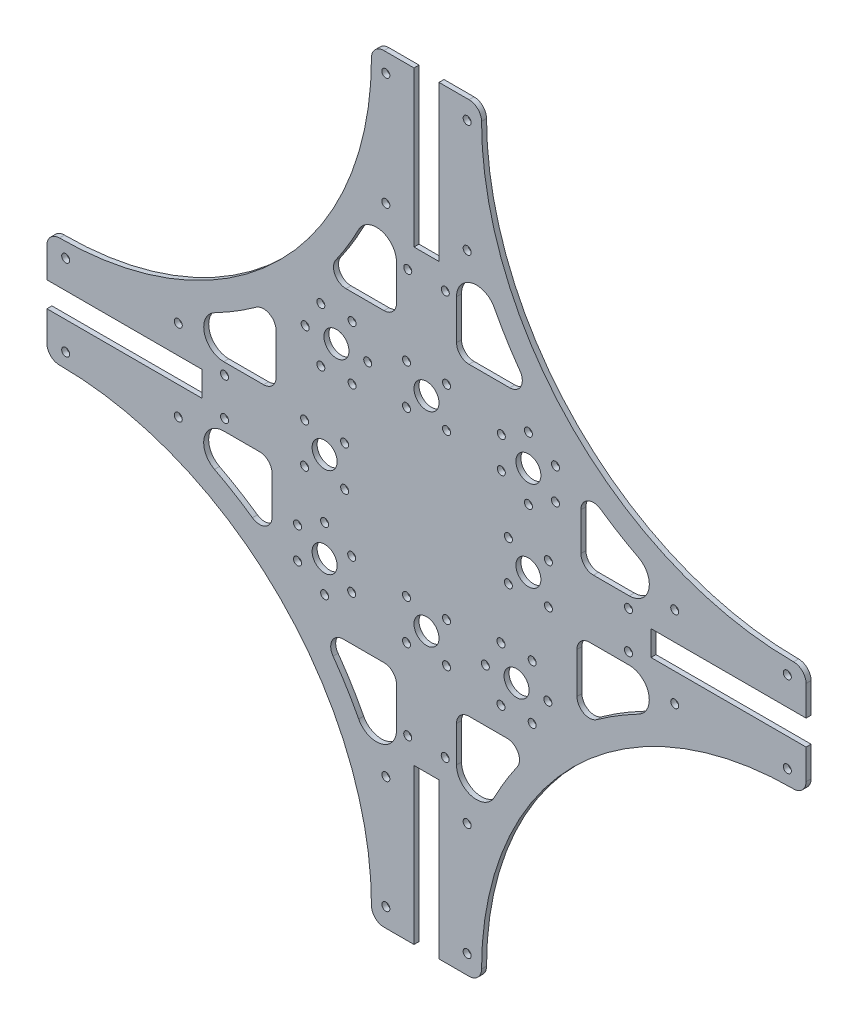
SolidWorks part; units mm, degrees
ref_plane "Front Plane" through (0, 0, 0) normal (0, 0, 1) x (1, 0, 0)
ref_plane "Top Plane" through (0, 0, 0) normal (0, 1, 0) x (1, 0, 0)
ref_plane "Right Plane" through (0, 0, 0) normal (1, 0, 0) x (0, 0, -1)
sketch "Sketch1" plane through (0, 0, 0) normal (0, 0, 1) x (1, 0, 0)
  line L0 (71.229, -85.5827) -> (71.229, -51.5827)
  line L1 (66.229, -90.5827) -> (-5.6672, -90.5827)
  line L2 (66.229, -46.5827) -> (-5.6672, -46.5827)
  line L3 (-102.5004, -215.312) -> (-102.5004, -143.4158)
  line L4 (-97.5004, -220.312) -> (-63.5004, -220.312)
  line L5 (-58.5004, -215.312) -> (-58.5004, -143.4158)
  line L6 (-227.2297, -46.5827) -> (-155.3335, -46.5827)
  line L7 (-232.2297, -51.5827) -> (-232.2297, -85.5827)
  line L8 (-227.2297, -90.5827) -> (-155.3335, -90.5827)
  line L9 (-58.5004, 78.1467) -> (-58.5004, 6.2505)
  line L10 (-63.5004, 83.1467) -> (-97.5004, 83.1467)
  line L11 (-102.5004, 78.1467) -> (-102.5004, 6.2505)
  arc A0 (-97.5004, -220.312) -> (-102.5004, -215.312) centre (-97.5004, -215.312) cw
  arc A1 (71.229, -51.5827) -> (66.229, -46.5827) centre (66.229, -51.5827) ccw
  arc A2 (71.229, -85.5827) -> (66.229, -90.5827) centre (66.229, -85.5827) cw
  arc A3 (-5.6672, -46.5827) -> (-58.5004, 6.2505) centre (-80.5004, -68.5827) ccw
  arc A4 (-63.5004, -220.312) -> (-58.5004, -215.312) centre (-63.5004, -215.312) ccw
  arc A5 (-232.2297, -51.5827) -> (-227.2297, -46.5827) centre (-227.2297, -51.5827) cw
  arc A6 (-232.2297, -85.5827) -> (-227.2297, -90.5827) centre (-227.2297, -85.5827) ccw
  arc A7 (-63.5004, 83.1467) -> (-58.5004, 78.1467) centre (-63.5004, 78.1467) cw
  arc A8 (-97.5004, 83.1467) -> (-102.5004, 78.1467) centre (-97.5004, 78.1467) ccw
  arc A9 (-102.5004, 6.2505) -> (-155.3335, -46.5827) centre (-80.5004, -68.5827) ccw
  arc A10 (-155.3335, -90.5827) -> (-102.5004, -143.4158) centre (-80.5004, -68.5827) ccw
  arc A11 (-58.5004, -143.4158) -> (-5.6672, -90.5827) centre (-80.5004, -68.5827) ccw
  point P14 (-80.5004, -68.5827)
  point P42 (-80.5004, -68.5827)
  dimension "D1" = 4
extrude "Boss-Extrude1" add sketch "Sketch1" along normal blind 2
sketch "Sketch2" plane through (0, 0, 2) normal (0, 0, 1) x (1, 0, 0)
  circle A1 centre (-39.771, -68.5827) radius 5
  circle A2 centre (-80.5004, -109.312) radius 5
  circle A3 centre (-121.2297, -68.5827) radius 5
  circle A4 centre (-80.5004, -27.8533) radius 5
  point P9 (-80.5004, -68.5827)
  point P19 (-80.5004, -68.5827)
  dimension "D1" = 4
  dimension "D3" = 10
  dimension "D2" = 57.6
extrude "Cut-Extrude1" cut sketch "Sketch2" against normal blind 2
ref_axis "A1" through (-80.5004, -109.312, 0) along (0, 0, 1)
ref_axis "A2" through (-39.771, -68.5827, 0) along (0, 0, 1)
ref_axis "A3" through (-121.2297, -68.5827, 0) along (0, 0, 1)
ref_axis "A4" through (-80.5004, -27.8533, 0) along (0, 0, 1)
ref_axis "Ось апп" through (-80.5004, -68.5827, 62.4812) along (0, 0, -1)
sketch "Sketch3" plane through (0, 0, 2) normal (0, 0, 1) x (1, 0, 0)
  line L0 (-39.771, -68.5827) -> (-39.771, -13.6018) construction
  circle A0 centre (-39.771, -32.5827) radius 5
  circle A3 centre (-39.771, -20.0827) radius 1.6
  circle A4 centre (-28.9457, -26.3327) radius 1.6
  circle A5 centre (-28.9457, -38.8327) radius 1.6
  circle A6 centre (-39.771, -45.0827) radius 1.6
  circle A7 centre (-50.5963, -38.8327) radius 1.6
  circle A8 centre (-50.5963, -26.3327) radius 1.6
  circle A21 centre (-39.771, -32.5827) radius 12.5 construction
  circle A22 centre (-44.5004, -109.312) radius 5
  circle A23 centre (-32.0004, -109.312) radius 1.6
  circle A24 centre (-38.2504, -120.1373) radius 1.6
  circle A25 centre (-50.7504, -120.1373) radius 1.6
  circle A26 centre (-57.0004, -109.312) radius 1.6
  circle A27 centre (-50.7504, -98.4867) radius 1.6
  circle A28 centre (-38.2504, -98.4867) radius 1.6
  circle A29 centre (-44.5004, -109.312) radius 12.5 construction
  circle A30 centre (-121.2297, -104.5827) radius 5
  circle A31 centre (-121.2297, -117.0827) radius 1.6
  circle A32 centre (-132.055, -110.8327) radius 1.6
  circle A33 centre (-132.055, -98.3327) radius 1.6
  circle A34 centre (-121.2297, -92.0827) radius 1.6
  circle A35 centre (-110.4044, -98.3327) radius 1.6
  circle A36 centre (-110.4044, -110.8327) radius 1.6
  circle A37 centre (-121.2297, -104.5827) radius 12.5 construction
  circle A38 centre (-116.5004, -27.8533) radius 5
  circle A39 centre (-129.0004, -27.8533) radius 1.6
  circle A40 centre (-122.7504, -17.028) radius 1.6
  circle A41 centre (-110.2504, -17.028) radius 1.6
  circle A42 centre (-104.0004, -27.8533) radius 1.6
  circle A43 centre (-110.2504, -38.6786) radius 1.6
  circle A44 centre (-122.7504, -38.6786) radius 1.6
  circle A45 centre (-116.5004, -27.8533) radius 12.5 construction
  point P9 (-80.5004, -68.5827)
  point P15 (-80.5004, -68.5827)
  point P28 (-39.771, -32.5827)
  point P40 (-80.5004, -68.5827)
  point P69 (-44.5004, -109.312)
  point P85 (-121.2297, -104.5827)
  point P101 (-116.5004, -27.8533)
  point P103 (-80.5004, -68.5827)
  dimension "D1" = 36
  dimension "D3" = 10
  dimension "D6" = 12.5
  dimension "D9" = 4
  dimension "D7" = 6
extrude "Cut-Extrude2" cut sketch "Sketch3" against normal blind 2
sketch "Sketch4" plane through (0, 0, 0) normal (0, 0, -1) x (-1, 0, 0)
  line L0 (232.2297, -63.5827) -> (170.2297, -63.5827)
  line L1 (232.2297, -51.5827) -> (232.2297, -85.5827) construction
  line L2 (170.2297, -63.5827) -> (170.2297, -73.5827)
  line L3 (170.2297, -73.5827) -> (232.2297, -73.5827)
  line L4 (232.2297, -73.5827) -> (232.2297, -63.5827)
  line L6 (227.2297, -90.5827) -> (155.3335, -90.5827) construction
  line L7 (155.3335, -46.5827) -> (227.2297, -46.5827) construction
  line L8 (102.5004, -143.4158) -> (58.5004, 6.2505) construction
  point P13 (80.5004, -68.5827)
  dimension "D1" = 17
  dimension "D2" = 17
  dimension "D3" = 62
extrude "Cut-Extrude3" cut sketch "Sketch4" against normal blind 2
pattern_circular "CirPattern1" count 4 over 360 about axis through (-80.5004, -68.5827, 62.4812) along (0, 0, -1) of "Cut-Extrude3"
sketch "Sketch5" plane through (0, 0, 2) normal (0, 0, 1) x (1, 0, 0)
  line L0 (66.229, -46.5827) -> (-5.6672, -46.5827)
  line L1 (-5.6672, -46.5827) -> (-58.5004, 6.2505)
  line L2 (-58.5004, 6.2505) -> (-58.5004, 78.1467)
  arc A0 (66.229, -46.5827) -> (-58.5004, 78.1467) centre (66.229, 78.1467) cw
extrude "Boss-Extrude2" add sketch "Sketch5" against normal blind 2
pattern_circular "CirPattern2" count 4 over 360 about axis through (-80.5004, -68.5827, 62.4812) along (0, 0, -1) of "Boss-Extrude2"
sketch "Sketch6" plane through (0, 0, 2) normal (0, 0, 1) x (1, 0, 0)
  line L0 (0.5682, -56.5827) -> (-13.771, -56.5827)
  line L1 (-68.491, -3.4418) -> (-68.491, 12.4678)
  line L2 (-18.771, -51.5827) -> (-18.771, -36.4146)
  line L3 (-47.2065, -8.4418) -> (-63.491, -8.4418)
  arc A0 (4.2485, -41.4795) -> (0.5682, -56.5827) centre (0.5682, -48.5827) cw
  arc A1 (4.2485, -41.4795) -> (-10.9083, -32.3152) centre (66.229, 78.1467) cw
  circle A2 centre (-72.5004, -19.8533) radius 1.6
  circle A4 centre (-72.5004, -35.8533) radius 1.6
  circle A5 centre (-88.5004, -35.8533) radius 1.6
  circle A6 centre (-88.5004, -19.8533) radius 1.6
  arc A7 (-43.1474, -0.5223) -> (-53.3883, 16.1491) centre (66.229, 78.1467) cw
  arc A8 (-47.2065, -8.4418) -> (-43.1474, -0.5223) centre (-47.2065, -3.4418) ccw
  arc A9 (-68.491, 12.4678) -> (-53.3883, 16.1491) centre (-60.491, 12.4678) cw
  arc A10 (-63.491, -8.4418) -> (-68.491, -3.4418) centre (-63.491, -3.4418) cw
  arc A13 (-18.771, -51.5827) -> (-13.771, -56.5827) centre (-13.771, -51.5827) ccw
  arc A14 (-18.771, -36.4146) -> (-10.9083, -32.3152) centre (-13.771, -36.4146) cw
  point P5 (-80.5004, -27.8533)
  point P6 (66.229, -56.5827)
  point P7 (-68.491, 76.5582)
  point P16 (-36.9913, -8.4418)
  point P26 (-80.5004, -27.8533)
  dimension "D1" = 8
  dimension "D4" = 8
  dimension "D5" = 8
  dimension "D7" = 5
  dimension "D8" = 8
  dimension "D2" = 85
  dimension "D3" = 85
  dimension "D6" = 4
extrude "Cut-Extrude4" cut sketch "Sketch6" against normal blind 2
pattern_circular "CirPattern3" count 4 over 360 about axis through (-80.5004, -68.5827, 62.4812) along (0, 0, -1) of "Cut-Extrude4"
sketch "Sketch7" plane through (0, 0, 2) normal (0, 0, 1) x (1, 0, 0)
  line L0 (0.5501, -80.592) -> (-15.3595, -80.592) construction
  circle A0 centre (0.229, -76.092) radius 1.6
  circle A1 centre (0.229, -61.092) radius 1.6
  circle A2 centre (63.729, -84.8327) radius 1.6
  circle A3 centre (63.729, -52.3327) radius 1.6
  circle A4 centre (18.729, -84.8327) radius 1.6
  circle A5 centre (18.729, -52.3327) radius 1.6
  dimension "D1" = 15
  dimension "D2" = 4.5
  dimension "D3" = 40
extrude "Cut-Extrude5" cut sketch "Sketch7" against normal blind 2
pattern_circular "CirPattern4" count 4 over 360 about axis through (-80.5004, -68.5827, 62.4812) along (0, 0, -1) of "Cut-Extrude5"
